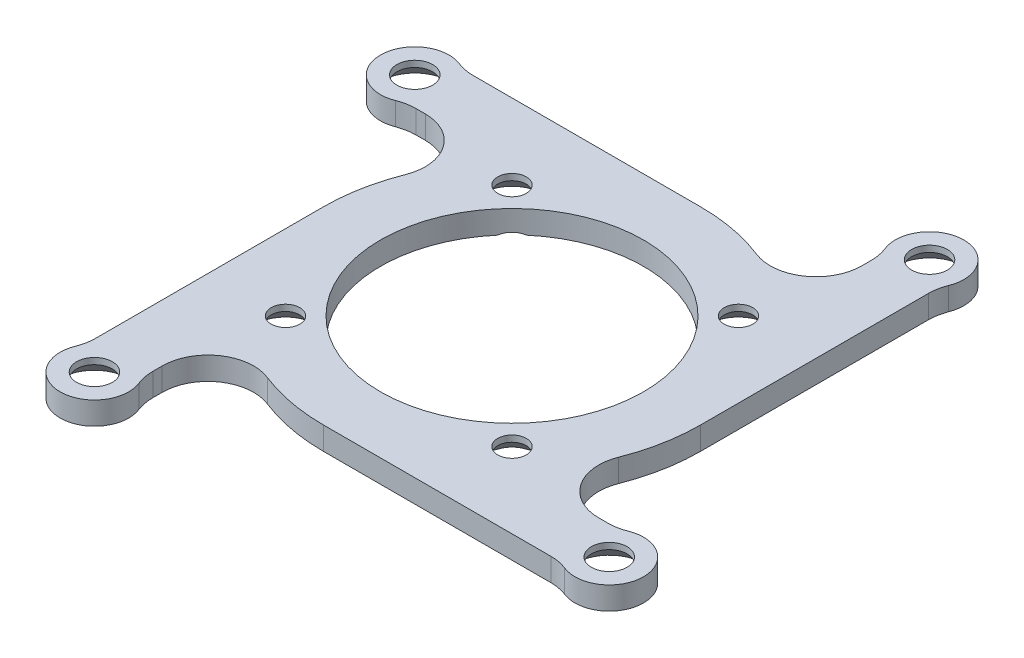
SolidWorks part; units mm, degrees
material "Cast Alloy Steel"
ref_plane "Front Plane" through (0, 0, 0) normal (0, 0, 1) x (1, 0, 0)
ref_plane "Top Plane" through (0, 0, 0) normal (0, 1, 0) x (1, 0, 0)
ref_plane "Right Plane" through (0, 0, 0) normal (1, 0, 0) x (0, 0, -1)
sketch "Sketch1" plane through (0, 0, 0) normal (0, 1, 0) x (1, 0, 0)
  line L0 (-19.799, -19.799) -> (19.799, 19.799) construction
  line L1 (-41.6834, 33) -> (0, 33)
  line L3 (33, 41.6834) -> (33, 0)
  line L5 (41.6834, -33) -> (0, -33)
  line L7 (-45, -10.4663) -> (-45, 24.875) construction
  line L8 (-45, 24.875) -> (-45, 31.125) construction
  line L9 (-45, 31.125) -> (-45, 33) construction
  line L10 (-16.2635, 16.2635) -> (-23.3345, 23.3345) construction
  line L11 (-33, -41.6834) -> (-33, 0)
  line L17 (23, 41.6834) -> (23, 23.6643)
  line L19 (41.6834, -23) -> (23.6643, -23)
  line L21 (-23, -41.6834) -> (-23, -23.6643)
  line L23 (-41.6834, 23) -> (-23.6643, 23)
  circle A0 centre (0, 0) radius 23
  circle A1 centre (-19.799, 19.799) radius 2.5
  circle A2 centre (19.799, 19.799) radius 2.5
  circle A3 centre (19.799, -19.799) radius 2.5
  circle A4 centre (-19.799, -19.799) radius 2.5
  circle A5 centre (0, 0) radius 28 construction
  arc A6 (23, 23.6643) -> (0, 33) centre (0, 0) ccw
  arc A7 (-45, 33) -> (-49.2453, 30.6415) centre (-45, 28) ccw construction
  arc A8 (33, 45) -> (30.6415, 49.2453) centre (28, 45) ccw construction
  arc A9 (45, -33) -> (49.2453, -30.6415) centre (45, -28) ccw construction
  circle A10 centre (-45, 28) radius 3.125
  circle A11 centre (28, 45) radius 3.125
  circle A12 centre (45, -28) radius 3.125
  arc A13 (23.6643, -23) -> (33, 0) centre (0, 0) ccw
  arc A14 (-23.6643, 23) -> (-33, 0) centre (0, 0) ccw
  circle A15 centre (0, 0) radius 58 construction
  arc A16 (-33, -45) -> (-30.6415, -49.2453) centre (-28, -45) ccw construction
  circle A17 centre (-28, -45) radius 3.125
  arc A18 (-23, -23.6643) -> (0, -33) centre (0, 0) ccw
  arc A19 (33, 41.6834) -> (23, 41.6834) centre (28, 45) ccw
  arc A20 (-41.6834, 33) -> (-41.6834, 23) centre (-45, 28) ccw
  arc A21 (-33, -41.6834) -> (-23, -41.6834) centre (-28, -45) ccw
  arc A22 (41.6834, -33) -> (41.6834, -23) centre (45, -28) ccw
  point P15 (-33, 0)
  point P33 (0, 0)
  point P77 (0, 0)
  dimension "D2" = 5
  dimension "D3" = 6.25
  dimension "D4" = 116
  dimension "D5" = 56
  dimension "D7" = 5
  dimension "D8" = 12
  dimension "D6" = 10
  dimension "D1" = 4
  dimension "D9" = 4
extrude "Boss-Extrude1" add sketch "Sketch1" along normal blind 4
fillet "Fillet1" radius 8 12 edges at (-23, 2, 23.6643) (-23.6643, 2, -23) (23.6643, 2, 23) (23, 2, -23.6643) (41.6834, 2, 23) (41.6834, 2, 33) (-23, 2, 41.6834) (-33, 2, 41.6834) (-41.6834, 2, -33) (-41.6834, 2, -23) (23, 2, -41.6834) (33, 2, -41.6834)
chamfer "Chamfer1" distance 2.9 angle 45 8 edges at (-45, 0, -24.875) (-28, 0, 48.125) (45, 0, 31.125) (28, 0, -41.875) (19.799, 0, -17.299) (19.799, 0, 22.299) (-19.799, 0, 22.299) (-19.799, 0, -17.299)
chamfer "Chamfer2" distance 1 angle 45 6 edges at (22.8924, 0, -41.1117) (23, 0, -38.9807) (19.5047, 0, -31.5464) (6.144, 0, -32.423) (-41.1117, 0, -33.1076) (-19.9019, 0, -33)
